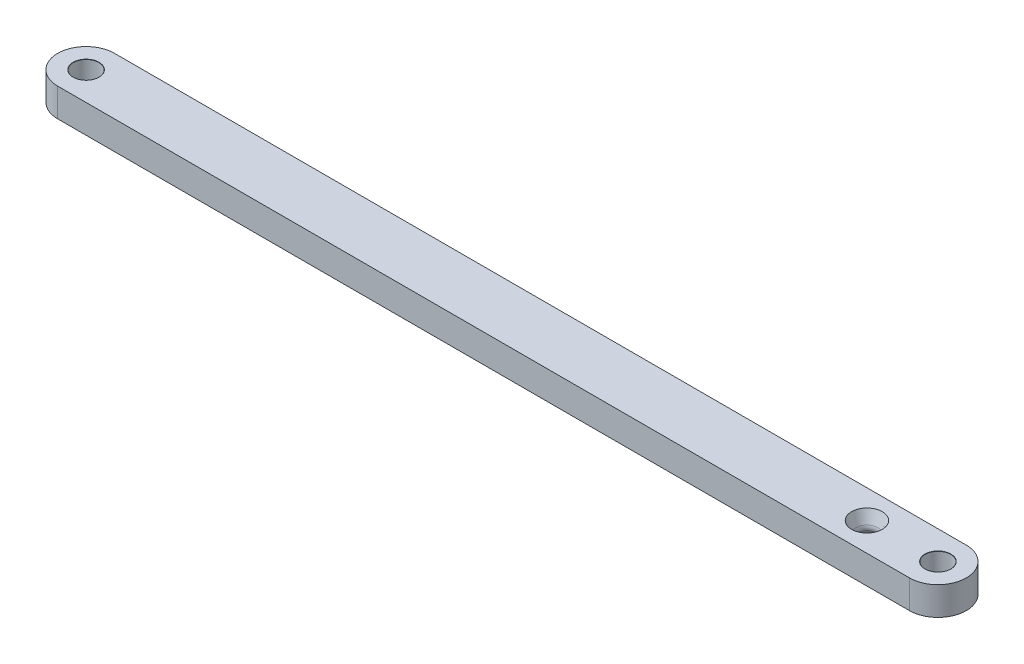
SolidWorks part; units mm, degrees
ref_plane "Front Plane" through (0, 0, 0) normal (0, 0, 1) x (1, 0, 0)
ref_plane "Top Plane" through (0, 0, 0) normal (0, 1, 0) x (1, 0, 0)
ref_plane "Right Plane" through (0, 0, 0) normal (1, 0, 0) x (0, 0, -1)
sketch "Sketch1" plane through (0, 0, 0) normal (0, 1, 0) x (1, 0, 0)
  line L0 (0, 0) -> (120, 0) construction
  line L1 (0, 4) -> (120, 4)
  line L2 (0, -4) -> (120, -4)
  arc A0 (0, 4) -> (0, -4) centre (0, 0) ccw
  arc A1 (120, -4) -> (120, 4) centre (120, 0) ccw
  circle A2 centre (0, 0) radius 1
  circle A3 centre (120, 0) radius 1
  circle A4 centre (110, 0) radius 1
  point P3 (60, 0)
  dimension "D3" = 2
  dimension "D4" = 2
  dimension "D6" = 2
  dimension "D1" = 8
  dimension "D2" = 120
  dimension "D5" = 10
extrude "Boss-Extrude1" add sketch "Sketch1" along normal mid plane 4
ref_axis "Axis1" through (110, 2, 0) along (0, -1, 0)
sketch "Sketch3" plane through (0, 0, 0) normal (0, 0, 1) x (1, 0, 0)
  line L0 (105.3308, 0) -> (117.0456, 0) construction
  line L1 (110, 2) -> (112.1638, 2)
  line L2 (110, 2) -> (110, -2) construction
  line L3 (0, 2) -> (120, 2) construction
  line L4 (112.1638, 2) -> (111.5603, 0.342)
  line L5 (110, -2) -> (112.1638, -2)
  line L6 (112.1638, -2) -> (111.5603, -0.342)
  line L7 (111.5, 2.8173) -> (111.5, -2.4487) construction
  line L8 (110, 2) -> (110, -2)
  arc A0 (111.5603, -0.342) -> (111.5603, 0.342) centre (112.5, 0) cw
  point P14 (111.4358, 0)
  dimension "D1" = 1
  dimension "D2" = 1.5
  dimension "D3" = 20
revolve "Cut-Revolve1" cut sketch "Sketch3" angle 360 about L8
hole_wizard "M3 Clearance Hole1" positions "Sketch4" profile "Sketch5" hole size "M3" standard "ANSI Metric" end condition through all
sketch "Sketch4" plane through (0, 2, 0) normal (0, 1, 0) x (1, 0, 0)
  point P4 (0, 0)
  point P7 (120, 0)
  point P11 (0, 0)
sketch "Sketch5" plane through (0, 2, 0) normal (1, 0, 0) x (0, 0, 1)
  line L0 (0, 0) -> (0, 4)
  line L1 (0, 4) -> (1.8, 4)
  line L2 (1.8, 4) -> (1.8, 0.025)
  line L3 (1.8, 0.025) -> (1.825, 0)
  line L5 (1.825, 0) -> (0, 0)
  line L6 (-1.8, 0.025) -> (-1.825, 0) construction
  line L11 (0, -6.35) -> (0, 107.95) construction
  dimension "Thru Hole Dia." = 3.6
  dimension "Thru Hole Depth" = 4
  dimension "Near C'Sink Dia." = 3.65
  dimension "Near C'Sink Angle" = 90
